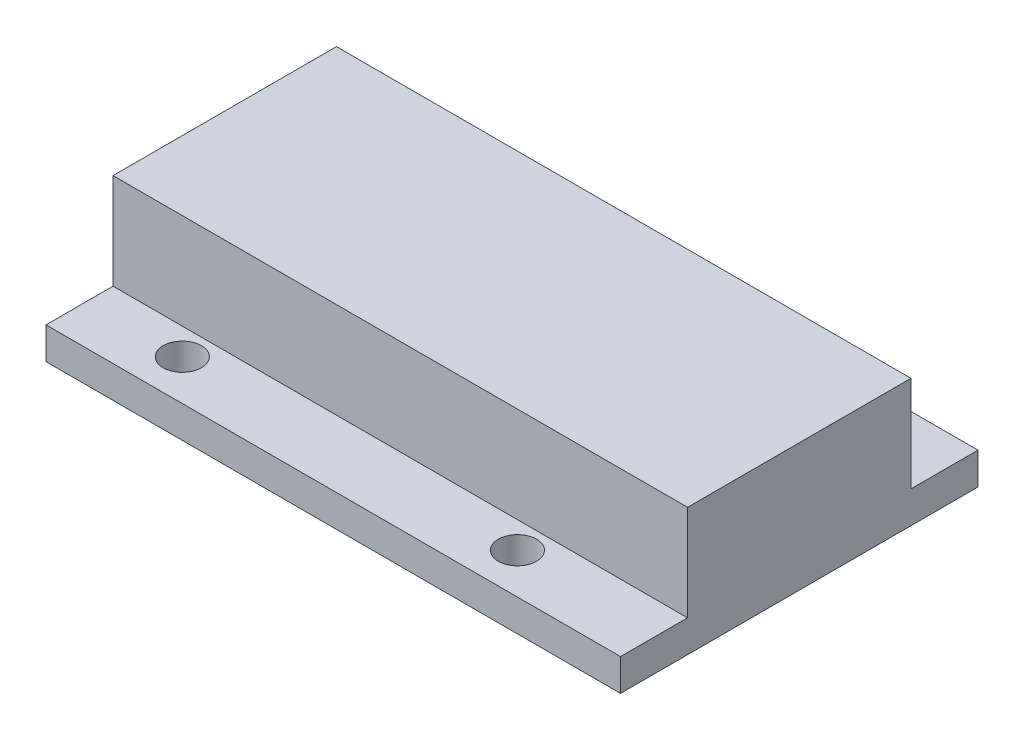
SolidWorks part; units mm, degrees
ref_plane "前视基准面" through (0, 0, 0) normal (0, 0, 1) x (1, 0, 0)
ref_plane "上视基准面" through (0, 0, 0) normal (0, 1, 0) x (1, 0, 0)
ref_plane "右视基准面" through (0, 0, 0) normal (1, 0, 0) x (0, 0, -1)
other "Configuration Table"
sketch "草图1" plane through (0, 0, 0) normal (1, 0, 0) x (0, 0, -1)
  line L0 (-5.6, 0) -> (5.6, 0)
  line L9 (-5.6, 0) -> (-5.6, 4)
  line L14 (-5.6, 4) -> (5.6, 4)
  line L15 (5.6, 4) -> (5.6, 0)
  line L16 (-3.5, 4) -> (-3.5, 0)
  line L17 (3.5, 4) -> (3.5, 0)
  line L18 (-5.6, 1) -> (-3.5, 1)
  line L19 (3.5, 1) -> (5.6, 1)
  circle A0 centre (0, 0) radius 3.1
  circle A2 centre (0, 0) radius 1.5
  dimension "D1" = 6.2
  dimension "D2" = 11.2
  dimension "D7" = 3
  dimension "D3" = 4
  dimension "D4" = 3.5
  dimension "D5" = 3.5
  dimension "D6" = 1
extrude "凸台-拉伸1" add sketch "草图1" against normal blind 18 contours A0 L0 L17 L14 L16 | L18 L9 L0 L16 | L19 L17 L0 L15 region at (0, 0.5, 4.55) region at (0, 0.5, 3.4194) region at (0, 0.5, -4.55)
extrude "凸台-拉伸2" add sketch "草图1<6>" against normal blind 5 contours A2 L0 A0 region at (0, 1.5233, 0)
sketch "草图1<6>" plane through (0, 0, 0) normal (1, 0, 0) x (0, 0, -1) same geometry as "草图1"
extrude "凸台-拉伸3" add sketch "草图1<7>" against normal blind 1 contours L0 A2 region at (0, 0.6366, 0)
sketch "草图1<7>" plane through (0, 0, 0) normal (1, 0, 0) x (0, 0, -1) same geometry as "草图1"
sketch "草图2" plane through (0, 0, 0) normal (0, -1, 0) x (1, 0, 0)
  circle A0 centre (-15, 4.3295) radius 0.6
  circle A1 centre (-4.5, 4.3295) radius 0.6
  circle A2 centre (-9, -4.4205) radius 0.6
  dimension "D1" = 1.2
extrude "切除-拉伸1" cut sketch "草图2" against normal through all contours A0 | A1 | A2
